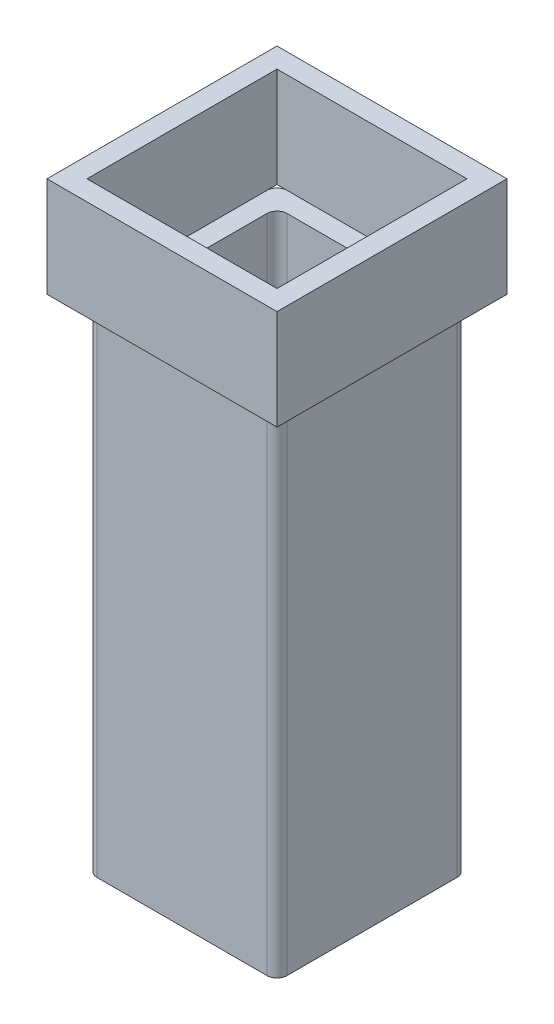
SolidWorks part; units mm, degrees
ref_plane "Alzado" through (0, 0, 0) normal (0, 0, 1) x (1, 0, 0)
ref_plane "Planta" through (0, 0, 0) normal (0, 1, 0) x (1, 0, 0)
ref_plane "Vista lateral" through (0, 0, 0) normal (1, 0, 0) x (0, 0, -1)
sketch "Croquis1" plane through (0, 0, 0) normal (0, 1, 0) x (1, 0, 0)
  line L1 (7.5, 7.5) -> (-7.5, 7.5)
  line L2 (7.5, 7.5) -> (7.5, -7.5)
  line L3 (7.5, -7.5) -> (-7.5, -7.5)
  line L4 (-7.5, 7.5) -> (-7.5, -7.5)
  line L5 (7.5, 7.5) -> (-7.5, -7.5) construction
  line L6 (7.5, -7.5) -> (-7.5, 7.5) construction
  line L7 (9.5, 9.5) -> (-9.5, 9.5)
  line L8 (9.5, 9.5) -> (9.5, -9.5)
  line L9 (9.5, -9.5) -> (-9.5, -9.5)
  line L10 (-9.5, 9.5) -> (-9.5, -9.5)
  line L11 (9.5, 9.5) -> (-9.5, -9.5) construction
  line L12 (9.5, -9.5) -> (-9.5, 9.5) construction
  point P0 (0, 0)
  point P6 (0, 0)
  dimension "D1" = 2
  dimension "D2" = 15
extrude "Saliente-Extruir1" add sketch "Croquis1" along normal blind 50
sketch "Croquis2" plane through (0, 50, 0) normal (0, 1, 0) x (1, 0, 0)
  line L1 (11.5, 11.5) -> (-11.5, 11.5)
  line L2 (11.5, 11.5) -> (11.5, -11.5)
  line L3 (11.5, -11.5) -> (-11.5, -11.5)
  line L4 (-11.5, 11.5) -> (-11.5, -11.5)
  line L5 (11.5, 11.5) -> (-11.5, -11.5) construction
  line L6 (11.5, -11.5) -> (-11.5, 11.5) construction
  line L7 (-9.5, 9.5) -> (9.5, 9.5)
  line L8 (-9.5, 9.5) -> (-9.5, -9.5)
  line L9 (-9.5, -9.5) -> (9.5, -9.5)
  line L10 (9.5, 9.5) -> (9.5, -9.5)
  point P0 (0, 0)
  dimension "D1" = 2
extrude "Saliente-Extruir2" add sketch "Croquis2" along normal blind 10 separate body
fillet "Redondeo1" radius 1 8 edges at (-7.5, 25, 7.5) (-7.5, 25, -7.5) (7.5, 25, -7.5) (7.5, 25, 7.5) (9.5, 25, 9.5) (-9.5, 25, 9.5) (-9.5, 25, -9.5) (9.5, 25, -9.5)
